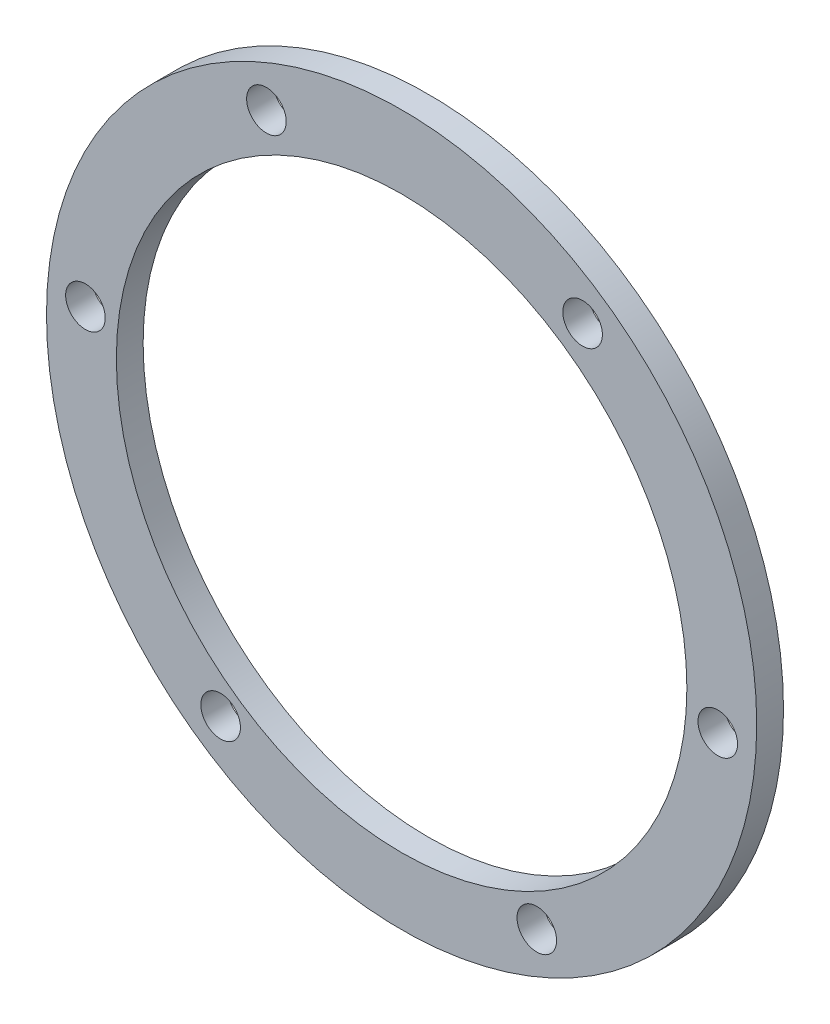
SolidWorks part; units mm, degrees
note: The reader was unsure of these and kept them because the rebuilt part matched: shared geometry of "Esquisse1<3>".
ref_plane "Plan de face" through (0, 0, 0) normal (0, 0, 1) x (1, 0, 0)
ref_plane "Plan de dessus" through (0, 0, 0) normal (0, 1, 0) x (1, 0, 0)
ref_plane "Plan de droite" through (0, 0, 0) normal (1, 0, 0) x (0, 0, -1)
sketch "Esquisse1" plane through (0, 0, 0) normal (0, 0, 1) x (1, 0, 0)
  circle A0 centre (0, -0.2601) radius 30.5
  circle A1 centre (0, -0.5255) radius 24.5
  circle A2 centre (0, 0) radius 27.0368
  circle A4 centre (15.5433, 22.1223) radius 1.7
  point P9 (15.5433, 22.1223)
  dimension "D1" = 49
  dimension "D2" = 61
  dimension "D3" = 3.4
extrude "Boss.-Extru.1" add sketch "Esquisse1" along normal blind 2.3 contours A0 A4 A2 | A4 A2 A1 | A2 A4 | A2 A4
extrude "Enlèv. mat.-Extru.2" cut sketch "Esquisse1<3>" along normal up to next contours A2 A4 | A2 A4
sketch "Esquisse1<3>" plane through (0, 0, 0) normal (0, 0, 1) x (1, 0, 0) same geometry as "Esquisse1"
pattern_circular "Répétition circulaire1" count 6 over 360 about axis through (0, -0.2601, 0) along (0, 0, 1) of "Enlèv. mat.-Extru.2"
extrude "Enlèv. mat.-Extru.3" cut sketch "Esquisse2" against normal through all both and the other way through all
sketch "Esquisse2" plane through (0, -0.2601, -52.7137) normal (0, 0, -1) x (0.0833, 0.9965, 0)
  line L0 (0, 0) -> (-310.0404, -664.8838)
  line L1 (-310.0404, -664.8838) -> (664.8838, 310.0404)
  line L2 (664.8838, 310.0404) -> (0, 0)
  line L3 (0, 0) -> (177.4217, -177.4217) construction
  line L4 (0, 0) -> (0, 165.156) construction
